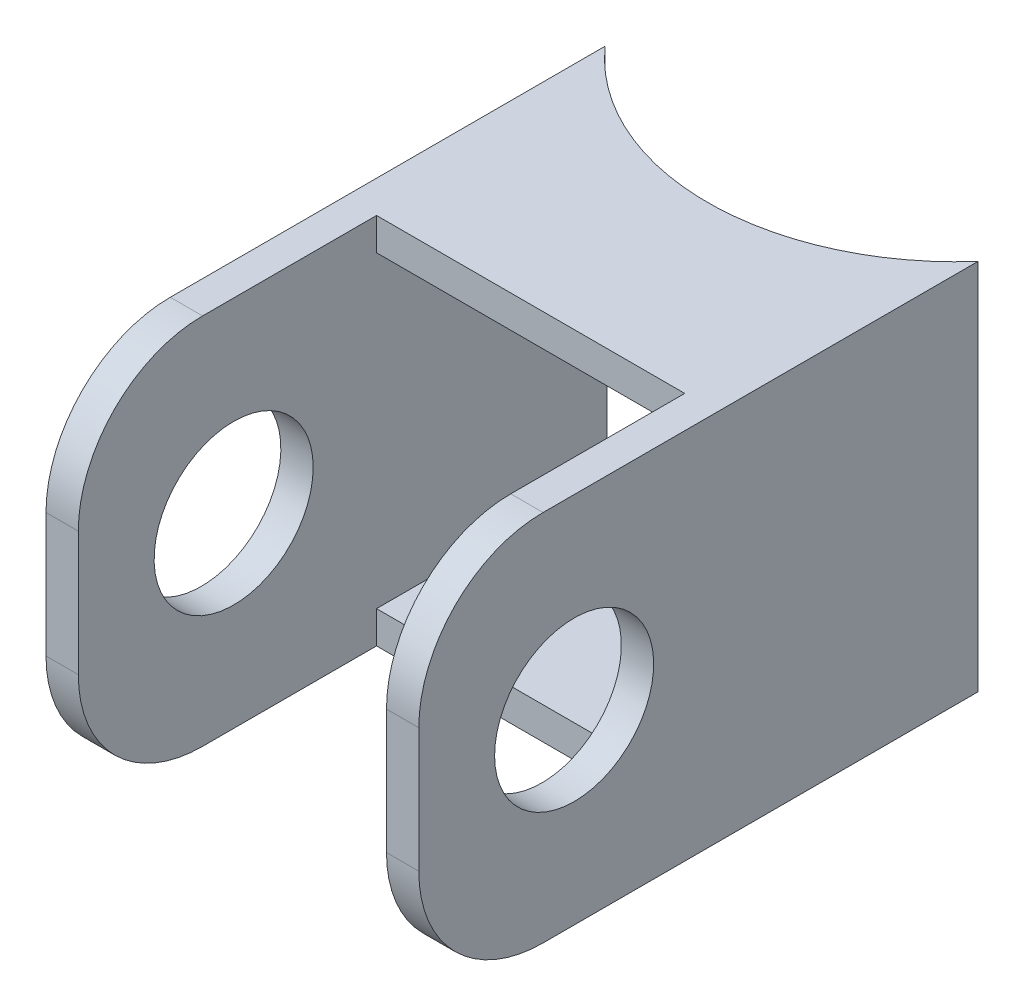
SolidWorks part; units mm, degrees
material "AISI 4130 Steel, annealed at 865C"
ref_plane "Front Plane" through (0, 0, 0) normal (0, 0, 1) x (1, 0, 0)
ref_plane "Top Plane" through (0, 0, 0) normal (0, 1, 0) x (1, 0, 0)
ref_plane "Right Plane" through (0, 0, 0) normal (1, 0, 0) x (0, 0, -1)
sketch "Sketch1" plane through (0, 0, 0) normal (0, 0, 1) x (1, 0, 0)
  line L1 (-9.525, 9.525) -> (9.525, 9.525)
  line L2 (-9.525, 9.525) -> (-9.525, -9.525)
  line L3 (-9.525, -9.525) -> (9.525, -9.525)
  line L4 (9.525, 9.525) -> (9.525, -9.525)
  line L5 (-9.525, 9.525) -> (9.525, -9.525) construction
  line L6 (-9.525, -9.525) -> (9.525, 9.525) construction
  line L7 (-7.874, 7.874) -> (7.874, 7.874)
  line L8 (-7.874, 7.874) -> (-7.874, -7.874)
  line L9 (-7.874, -7.874) -> (7.874, -7.874)
  line L10 (7.874, 7.874) -> (7.874, -7.874)
  line L11 (-7.874, 7.874) -> (7.874, -7.874) construction
  line L12 (-7.874, -7.874) -> (7.874, 7.874) construction
  point P0 (0, 0)
  point P6 (0, 0)
  dimension "D1" = 19.05
  dimension "D2" = 1.651
extrude "Boss-Extrude1" add sketch "Sketch1" along normal blind 28.575
sketch "Sketch5" plane through (0, 9.525, 0) normal (0, 1, 0) x (1, 0, 0)
  line L0 (0, -1000) -> (0, 49000) construction
  circle A0 centre (0, 8.4003) radius 12.7
  dimension "D1" = 25.4
extrude "Cut-Extrude5" cut sketch "Sketch5" against normal through all both and the other way through all
sketch "Sketch3" plane through (9.525, 0, 0) normal (1, 0, 0) x (0, 0, -1)
  line L0 (-28.575, -9.525) -> (0, -9.525) construction
  line L1 (-28.575, 9.525) -> (-20.6375, 9.525) construction
  line L2 (-28.575, 9.525) -> (-28.575, -9.525) construction
  line L3 (-28.575, -9.525) -> (-20.6375, -9.525) construction
  line L4 (-20.6375, 9.525) -> (-20.6375, -9.525) construction
  line L5 (-24.6062, -9.525) -> (-24.6062, 9.525) construction
  line L6 (-28.575, 0) -> (-20.6375, 0) construction
  circle A0 centre (-20.6375, 0) radius 4.064
  point P168 (-24.6062, 0)
  dimension "D1" = 8.128
  dimension "D2" = 7.9375
extrude "Cut-Extrude2" cut sketch "Sketch3" against normal through all both and the other way through all
sketch "Sketch4" plane through (0, -9.525, 0) normal (0, -1, 0) x (1, 0, 0)
  line L1 (-7.874, 28.575) -> (7.874, 28.575)
  line L2 (-7.874, 28.575) -> (-7.874, 13.335)
  line L3 (-7.874, 13.335) -> (7.874, 13.335)
  line L4 (7.874, 28.575) -> (7.874, 13.335)
  line L5 (0, 13.335) -> (0, 28.575) construction
  line L6 (-7.874, 20.955) -> (7.874, 20.955) construction
  line L7 (7.874, 24.7015) -> (7.874, 16.5735) construction
  point P96 (0, 20.955)
  dimension "D1" = 15.24
extrude "Cut-Extrude4" cut sketch "Sketch4" against normal through all both and the other way through all
fillet "Fillet2" radius 6.35 4 edges at (-8.6995, 9.525, 28.575) (8.6995, 9.525, 28.575) (-8.6995, -9.525, 28.575) (8.6995, -9.525, 28.575)
ref_axis "Axis2" through (-9.525, 0, 20.6375) along (1, 0, 0)
ref_point "Point2"
ref_axis "Axis3" through (0, 0, 0) along (0, 0, 1)
